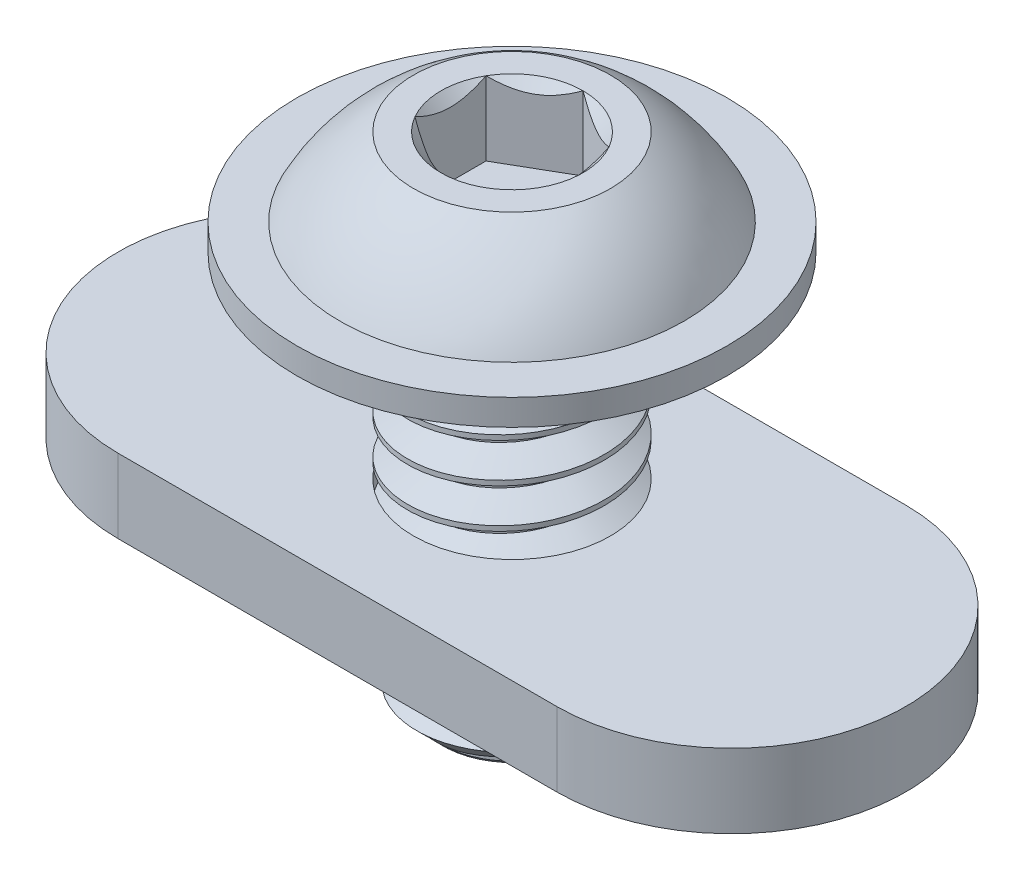
SolidWorks part; units mm, degrees
ref_plane "Front Plane" through (0, 0, 0) normal (0, 0, 1) x (1, 0, 0)
ref_plane "Top Plane" through (0, 0, 0) normal (0, 1, 0) x (1, 0, 0)
ref_plane "Right Plane" through (0, 0, 0) normal (1, 0, 0) x (0, 0, -1)
sketch "Sketch1" plane through (0, 0, 0) normal (0, 1, 0) x (1, 0, 0)
  circle A0 centre (0, 0) radius 3.175
  point P3 (-3.175, 0)
  point P4 (3.175, 0)
  dimension "D1" = 6.35
extrude "Boss-Extrude1" add sketch "Sketch1" against normal blind 12.7
sketch "Sketch2" plane through (0, -12.7, 0) normal (0, -1, 0) x (1, 0, 0)
  circle A1 centre (0, 0) radius 3.175
  circle A2 centre (0, 0) radius 3.175
  point P0 (0, -3.175)
  dimension "D1" = 0
curve "Helix/Spiral1" pitch 1.27 height 13.97 turns 11
sketch "Sketch3" plane through (0, 0, 0) normal (1, 0, 0) x (0, 0, -1)
  line L0 (3.3125, -12.6206) -> (2.2126, -13.2556) construction
  line L1 (2.2126, -13.2556) -> (3.3125, -13.8906) construction
  line L2 (3.3125, -13.8906) -> (3.3125, -12.6206) construction
  line L3 (2.3501, -13.1762) -> (2.3501, -13.335) construction
  line L4 (3.175, -12.7) -> (3.175, -13.8112) construction
  line L5 (2.2126, -13.2556) -> (2.3501, -13.2556) construction
  line L6 (3.175, -13.2556) -> (3.3125, -13.2556) construction
  line L8 (2.2126, -13.2556) -> (-3.175, -13.2556) construction
  line L9 (2.3501, -13.1762) -> (3.2437, -12.6603)
  line L10 (2.3501, -13.1762) -> (2.3501, -13.335)
  line L11 (2.3501, -13.335) -> (3.2437, -13.8509)
  line L12 (3.2437, -13.8509) -> (3.2437, -12.6603)
  line L14 (-3.175, -13.2556) -> (-3.175, -11.9856) construction
  line L15 (-3.175, -11.9856) -> (-3.175, -10.7156) construction
  line L16 (-3.175, -10.7156) -> (-3.175, -9.4456) construction
  line L17 (-3.175, -9.4456) -> (-3.175, -8.1756) construction
  line L18 (-3.175, 0) -> (-3.175, -12.7) construction
  point P15 (3.2437, -13.2556)
  dimension "D1" = 1.27
  dimension "D2" = 0.1588
sweep "Cut-Sweep1" cut profiles "Sketch3" path "Helix/Spiral1" align with end faces yes
sketch "Sketch4" plane through (0, -12.7, 0) normal (0, -1, 0) x (1, 0, 0)
  circle A0 centre (0, 0) radius 2.2126
extrude "Cut-Extrude1" cut sketch "Sketch4" against normal blind 1.27 draft 45 flip side to cut
sketch "Sketch5" plane through (0, 0, 0) normal (0, 0, 1) x (1, 0, 0)
  line L0 (0, 0) -> (0, 3.3528)
  line L1 (-6.9342, 0) -> (0, 0)
  line L2 (0, 3.3528) -> (-3.175, 3.3528)
  line L3 (-5.5499, 0.8382) -> (-6.9342, 0.8382)
  line L4 (-6.9342, 0.8382) -> (-6.9342, 0)
  line L5 (0, 0) -> (0, -12.7) construction
  arc A0 (-3.175, 3.3528) -> (-5.5499, 0.8382) centre (0, -2.0246) ccw
  dimension "D1" = 3.3528
  dimension "D2" = 0.8382
  dimension "D3" = 13.8684
  dimension "D4" = 11.0998
revolve "Revolve1" add sketch "Sketch5" angle 360 mid plane about L0
sketch "Sketch6" plane through (0, 3.3528, 0) normal (0, 1, 0) x (1, 0, 0)
  line L1 (0, 2.2914) -> (-1.9844, 1.1457)
  line L2 (-1.9844, 1.1457) -> (-1.9844, -1.1457)
  line L3 (-1.9844, -1.1457) -> (0, -2.2914)
  line L4 (0, -2.2914) -> (1.9844, -1.1457)
  line L5 (1.9844, -1.1457) -> (1.9844, 1.1457)
  line L6 (1.9844, 1.1457) -> (0, 2.2914)
  circle A0 centre (0, 0) radius 1.9844 construction
  dimension "D1" = 3.9688
extrude "Cut-Extrude2" cut sketch "Sketch6" against normal blind 2.3813
sketch "Sketch7" plane through (0, 3.3528, 0) normal (0, 1, 0) x (1, 0, 0)
  circle A0 centre (0, 0) radius 2.2914
extrude "Cut-Extrude3" cut sketch "Sketch7" against normal blind 2.3813 draft 45
sketch "Sketch8" plane through (0, 0, 0) normal (0, 1, 0) x (1, 0, 0)
  line L0 (-7.0739, 0) -> (7.0739, 0) construction
  line L1 (-7.0739, 5.6261) -> (7.0739, 5.6261)
  line L2 (-7.0739, -5.6261) -> (7.0739, -5.6261)
  line L4 (-12.7, 5.6261) -> (12.7, 5.6261) construction
  line L5 (-12.7, 5.6261) -> (-12.7, -5.6261) construction
  line L6 (-12.7, -5.6261) -> (12.7, -5.6261) construction
  line L7 (12.7, 5.6261) -> (12.7, -5.6261) construction
  arc A0 (-7.0739, 5.6261) -> (-7.0739, -5.6261) centre (-7.0739, 0) ccw
  arc A1 (7.0739, -5.6261) -> (7.0739, 5.6261) centre (7.0739, 0) ccw
  circle A3 centre (0, 0) radius 3.175
  circle A4 centre (0, 0) radius 3.175
  point P2 (0, 0)
  dimension "D2" = 25.4
  dimension "D3" = 11.2522
  dimension "D1" = 0
extrude "Boss-Extrude2" add sketch "Sketch8" against normal blind 2.3876 from offset 6.35 separate body offset against normal yes
sketch "Sketch9" plane through (0, -8.7376, 0) normal (0, -1, 0) x (1, 0, 0)
  circle A1 centre (0, 0) radius 3.175 construction
  circle A2 centre (0, 0) radius 3.175
  circle A3 centre (0, 0) radius 3.5687
  dimension "D1" = 7.1374
extrude "Boss-Extrude3" add sketch "Sketch9" along normal blind 0.762
sketch "SketchZ" plane through (0, 0, 0) normal (0, 0, 1) x (1, 0, 0)
  line L0 (3.175, -12.9381) -> (3.175, -11.6681) construction
  line L2 (0, -13.2556) -> (0, -11.9856) construction
  line L4 (3.175, -12.9381) -> (0, -12.9381) construction
  line L5 (0, -9.4456) -> (0, -8.1756) construction
  line L6 (0, -12.6206) -> (0, -13.2556) construction
equation "\"D3@Helix/Spiral1\" = \"D4@Helix/Spiral1\" + \"D1@Boss-Extrude1\""
equation "\"D1@Sketch3\" = \"D4@Helix/Spiral1\""
equation "\"D2@Sketch3\" = \"D1@Sketch3\" / 8"
equation "\"D1@Cut-Extrude1\" = \"D4@Helix/Spiral1\""
equation "\"D1@Cut-Extrude2\" = \"D1@Sketch6\" * 3/5"
equation "\"D1@Cut-Extrude3\" = \"D1@Cut-Extrude2\""
equation "\"D2@Sketch5\" = \"D1@Sketch5\" * 1/4"
